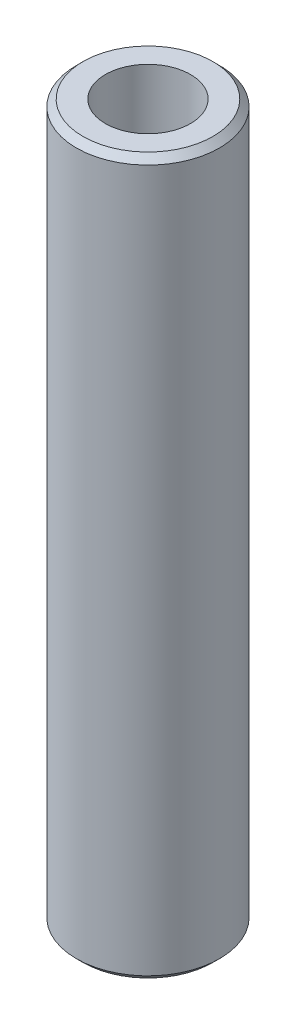
SolidWorks part; units mm, degrees
ref_plane "Front Plane" through (0, 0, 0) normal (0, 0, 1) x (1, 0, 0)
ref_plane "Top Plane" through (0, 0, 0) normal (0, 1, 0) x (1, 0, 0)
ref_plane "Right Plane" through (0, 0, 0) normal (1, 0, 0) x (0, 0, -1)
sketch "Sketch1" plane through (0, 0, 0) normal (0, 1, 0) x (1, 0, 0)
  circle A0 centre (0, 0) radius 60
  dimension "SHAFT_OD" = 120
extrude "Boss-Extrude1" add sketch "Sketch1" along normal blind 600
sketch "Sketch2" plane through (0, 0, 0) normal (0, 1, 0) x (1, 0, 0)
  circle A0 centre (0, 0) radius 35.6992
  dimension "BORE_D" = 71.3983
extrude "Cut-Extrude1" cut sketch "Sketch2" along normal through all
chamfer "Chamfer1" distance 5.5841 angle 44.707 2 edges at (0, 600, 60) (0, 0, 60) first distance on face at (0, 600, 60) first distance on face at (0, 0, 35.6992)
